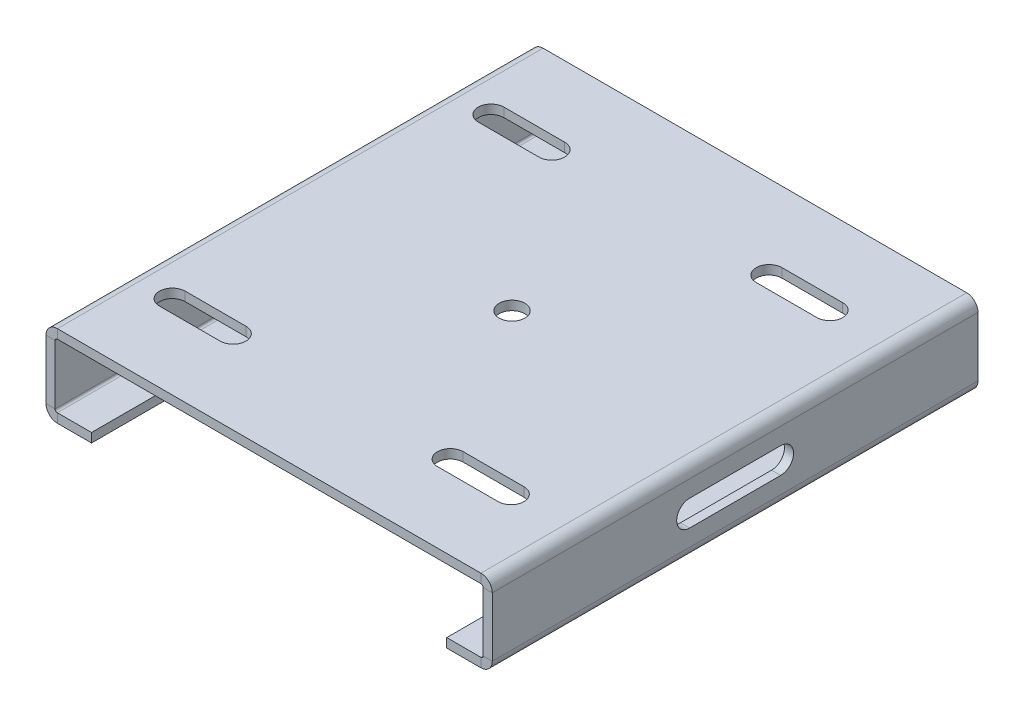
SolidWorks part; units mm, degrees
note: The reader was unsure of these and kept them because the rebuilt part matched: flange length of "Edge-Flange6", "Edge-Flange8".
ref_plane "Front Plane" through (0, 0, 0) normal (0, 0, 1) x (1, 0, 0)
ref_plane "Top Plane" through (0, 0, 0) normal (0, 1, 0) x (1, 0, 0)
ref_plane "Right Plane" through (0, 0, 0) normal (1, 0, 0) x (0, 0, -1)
sketch "Sketch1" plane through (0, 0, 0) normal (0, 1, 0) x (1, 0, 0)
  line L1 (-70.5, -80) -> (70.5, -80)
  line L2 (-70.5, -80) -> (-70.5, 80)
  line L3 (-70.5, 80) -> (70.5, 80)
  line L4 (70.5, -80) -> (70.5, 80)
  line L5 (-70.5, -80) -> (70.5, 80) construction
  line L6 (-70.5, 80) -> (70.5, -80) construction
  point P0 (0, 0)
  dimension "D1" = 141
  dimension "D2" = 160
base flange "Base-Flange3" sketch "Sketch1" thickness 3 reverse thickness direction no parameters "D1"=0.7366
edge flange "Edge-Flange6" sketch "Sketch58" flange profiles "Sketch58", "Sketch59" flange angle 90 flange length 24 flange position material outside bend radius 0.7366 thickness 3 relief rectangular parameters "D6"=10, "D8"=1
sketch "Sketch58" plane through (-70.5, -3, 0) normal (-1, 0, 0) x (0, 0, -1)
  line L0 (80, 0) -> (-80, 0) construction
  line L1 (80, 0) -> (-80, 0)
  line L2 (-80, 0) -> (-80, 21)
  line L3 (-80, 21) -> (80, 21)
  line L4 (80, 21) -> (80, 0)
sketch "Sketch59" plane through (70.5, -3, 0) normal (1, 0, 0) x (0, 0, 1)
  line L0 (80, 0) -> (-80, 0) construction
  line L1 (80, 0) -> (-80, 0)
  line L2 (-80, 0) -> (-80, 21)
  line L3 (-80, 21) -> (80, 21)
  line L4 (80, 21) -> (80, 0)
bend "EdgeBend11" bend radius 0.7366 bend angle 90 parameters "D5"=1
bend "EdgeBend12" bend radius 0.7366 bend angle 90 parameters "D5"=2
edge flange "Edge-Flange8" sketch "Sketch72" flange profiles "Sketch72", "Sketch73" flange angle 90 flange length 12 flange position material outside bend radius 0.7366 thickness 3 relief rectangular parameters "D6"=10, "D8"=1
sketch "Sketch72" plane through (-70.5, -24, 0) normal (0, -1, 0) x (0, 0, -1)
  line L0 (80, 0) -> (-80, 0) construction
  line L1 (80, 0) -> (-80, 0)
  line L2 (-80, 0) -> (-80, 12)
  line L3 (-80, 12) -> (80, 12)
  line L4 (80, 12) -> (80, 0)
sketch "Sketch73" plane through (70.5, -24, 0) normal (0, -1, 0) x (0, 0, 1)
  line L0 (80, 0) -> (-80, 0) construction
  line L1 (80, 0) -> (-80, 0)
  line L2 (-80, 0) -> (-80, 12)
  line L3 (-80, 12) -> (80, 12)
  line L4 (80, 12) -> (80, 0)
bend "EdgeBend15" bend radius 0.7366 bend angle 90 parameters "D5"=3
bend "EdgeBend16" bend radius 0.7366 bend angle 90 parameters "D5"=4
sketch "Sketch76" plane through (-73.5, 0, 0) normal (-1, 0, 0) x (0, 0, 1)
  line L0 (-15, -9.25) -> (15, -9.25)
  line L1 (-15, -17.75) -> (15, -17.75)
  circle A0 centre (-15, -13.5) radius 4.25
  circle A1 centre (15, -13.5) radius 4.25
extrude "Cut-Extrude1" cut sketch "Sketch76" against normal blind 10 contours A0 | A1 L0 A0 L1 | A1 normal cut yes
sketch "Sketch80" plane through (73.5, 0, 0) normal (1, 0, 0) x (0, 0, -1)
  line L0 (-15, -9.25) -> (15, -9.25)
  line L5 (-15, -17.75) -> (15, -17.75)
  circle A0 centre (-15, -13.5) radius 4.25
  circle A1 centre (15, -13.5) radius 4.25
extrude "Cut-Extrude3" cut sketch "Sketch80" against normal blind 10 contours A0 | A1 L0 A0 L5 | A1 normal cut yes
sketch "Sketch84" plane through (0, 0, 0) normal (0, 1, 0) x (1, 0, 0)
  line L4 (42.1906, -52.5) -> (32.1906, -52.5)
  line L5 (42.1906, -52.5) -> (52.1906, -52.5)
  line L6 (-59.3847, -56.75) -> (-39.3847, -56.75)
  line L7 (-59.3847, -48.25) -> (-39.3847, -48.25)
  line L8 (32.1906, -56.75) -> (52.1906, -56.75)
  line L9 (32.1906, -48.25) -> (52.1906, -48.25)
  line L12 (-59.3847, 48.25) -> (-39.3847, 48.25)
  line L13 (-59.3847, 56.75) -> (-39.3847, 56.75)
  line L16 (32.1906, 48.25) -> (52.1906, 48.25)
  line L17 (32.1906, 56.75) -> (52.1906, 56.75)
  circle A0 centre (-59.3847, -52.5) radius 4.25
  circle A1 centre (-39.3847, -52.5) radius 4.25
  circle A2 centre (32.1906, -52.5) radius 4.25
  circle A3 centre (52.1906, -52.5) radius 4.25
  circle A4 centre (-59.3847, 52.5) radius 4.25
  circle A5 centre (-39.3847, 52.5) radius 4.25
  circle A6 centre (32.1906, 52.5) radius 4.25
  circle A7 centre (52.1906, 52.5) radius 4.25
extrude "Cut-Extrude4" cut sketch "Sketch84" against normal blind 10
sketch "Sketch85" plane through (0, -3, 0) normal (0, -1, 0) x (1, 0, 0)
  line L0 (-70.5, -80) -> (70.5, 80) construction
  circle A0 centre (0, 0) radius 4.25
extrude "Cut-Extrude5" cut sketch "Sketch85" against normal blind 10 normal cut yes
sketch "Bend-Lines5" [suppressed] plane through (0, 0, 0) normal (0, 1, 0) x (1, 0, 0)
sketch "Bounding-Box5" [suppressed] plane through (0, 0, 0) normal (0, 1, 0) x (1, 0, 0)
sheet metal parameters "Sheet-Metal7" thickness 3 parameters "D1"=0.7366
flat pattern "Flat-Pattern7" [suppressed]
sketch "Bend-Lines6" plane through (0, 0, 0) normal (0, 1, 0) x (1, 0, 0)
sketch3d "Bounding-Box6" [suppressed]
  line L0 (-70.5, -80, 0) -> (-70.5, 80, 0) construction
  line L1 (70.5, -80, 0) -> (70.5, 80, 0) construction
  line L2 (-70.5, -80, 0) -> (70.5, -80, 0) construction
  line L3 (-70.5, 80, 0) -> (70.5, 80, 0) construction
sheet metal parameters "Sheet-Metal9" thickness 3 parameters "D1"=0.7366
flat pattern "Flat-Pattern7"
sketch "Bend-Lines6" plane through (0, 0, 0) normal (0, 1, 0) x (1, 0, 0)
  line L0 (71.52, -80) -> (71.52, 80) construction
  line L1 (-71.52, 80) -> (-71.52, -80) construction
  line L2 (71.52, -80) -> (71.52, 80) construction
  line L3 (-71.52, 80) -> (-71.52, -80) construction
sketch3d "Bounding-Box6" [suppressed]
  line L0 (93.54, 80, 0) -> (-93.54, 80, 0) construction
  line L1 (93.54, -80, 0) -> (-93.54, -80, 0) construction
  line L2 (93.54, 80, 0) -> (93.54, -80, 0) construction
  line L3 (-93.54, 80, 0) -> (-93.54, -80, 0) construction
bend of the flat pattern "Flatten-<EdgeBend11>1"
bend of the flat pattern "Flatten-<EdgeBend12>1"
sheet metal parameters "Sheet-Metal11" thickness 3 parameters "D1"=0.7366
flat pattern "Flat-Pattern7"
sketch "Bend-Lines6" plane through (0, 0, 0) normal (0, 1, 0) x (1, 0, 0)
  line L0 (71.52, -80) -> (71.52, 80) construction
  line L1 (-71.52, 80) -> (-71.52, -80) construction
  line L2 (71.52, -80) -> (71.52, 80) construction
  line L3 (-71.52, 80) -> (-71.52, -80) construction
  line L4 (94.5601, -80) -> (94.5601, 80) construction
  line L5 (-94.5601, 80) -> (-94.5601, -80) construction
  line L6 (94.5601, -80) -> (94.5601, 80) construction
  line L7 (-94.5601, 80) -> (-94.5601, -80) construction
sketch3d "Bounding-Box6" [suppressed]
  line L0 (107.5801, 80, 0) -> (-107.5801, 80, 0) construction
  line L1 (107.5801, -80, 0) -> (-107.5801, -80, 0) construction
  line L2 (107.5801, 80, 0) -> (107.5801, -80, 0) construction
  line L3 (-107.5801, 80, 0) -> (-107.5801, -80, 0) construction
bend of the flat pattern "Flatten-<EdgeBend11>1"
bend of the flat pattern "Flatten-<EdgeBend12>1"
bend of the flat pattern "Flatten-<EdgeBend15>1"
bend of the flat pattern "Flatten-<EdgeBend16>1"
sheet metal parameters "Sheet-Metal12" thickness 3 parameters "D1"=0.7366
flat pattern "Flat-Pattern7" [suppressed]
sketch "Bend-Lines6" plane through (0, 0, 0) normal (0, 1, 0) x (1, 0, 0)
  line L0 (71.52, -80) -> (71.52, 80) construction
  line L1 (-71.52, 80) -> (-71.52, -80) construction
  line L2 (71.52, -80) -> (71.52, 80) construction
  line L3 (-71.52, 80) -> (-71.52, -80) construction
  line L4 (94.5601, -80) -> (94.5601, 80) construction
  line L5 (-94.5601, 80) -> (-94.5601, -80) construction
  line L6 (94.5601, -80) -> (94.5601, 80) construction
  line L7 (-94.5601, 80) -> (-94.5601, -80) construction
sketch3d "Bounding-Box6" [suppressed]
  line L0 (107.5801, 80, 0) -> (-107.5801, 80, 0) construction
  line L1 (107.5801, -80, 0) -> (-107.5801, -80, 0) construction
  line L2 (107.5801, 80, 0) -> (107.5801, -80, 0) construction
  line L3 (-107.5801, 80, 0) -> (-107.5801, -80, 0) construction
bend of the flat pattern "Flatten-<EdgeBend11>1"
bend of the flat pattern "Flatten-<EdgeBend12>1"
bend of the flat pattern "Flatten-<EdgeBend15>1"
bend of the flat pattern "Flatten-<EdgeBend16>1"
sketch "Sketch80-1" [suppressed] plane through (69.54, 0, 0) normal (0, 1, 0) x (0, 0, -1)
  line L0 (-15, -9.25) -> (15, -9.25)
  line L5 (-15, -17.75) -> (15, -17.75)
  circle A0 centre (-15, -13.5) radius 4.25
  circle A1 centre (15, -13.5) radius 4.25
sheet metal parameters "Sheet-Metal14" thickness 3 parameters "D1"=0.7366
flat pattern "Flat-Pattern7" [suppressed]
sketch "Bend-Lines6" plane through (0, 0, 0) normal (0, 1, 0) x (1, 0, 0)
  line L0 (71.52, -80) -> (71.52, 80) construction
  line L1 (-71.52, 80) -> (-71.52, -80) construction
  line L2 (71.52, -80) -> (71.52, 80) construction
  line L3 (-71.52, 80) -> (-71.52, -80) construction
  line L4 (94.5601, -80) -> (94.5601, 80) construction
  line L5 (-94.5601, 80) -> (-94.5601, -80) construction
  line L6 (94.5601, -80) -> (94.5601, 80) construction
  line L7 (-94.5601, 80) -> (-94.5601, -80) construction
sketch3d "Bounding-Box6" [suppressed]
  line L0 (107.5801, 80, 0) -> (-107.5801, 80, 0) construction
  line L1 (107.5801, -80, 0) -> (-107.5801, -80, 0) construction
  line L2 (107.5801, 80, 0) -> (107.5801, -80, 0) construction
  line L3 (-107.5801, 80, 0) -> (-107.5801, -80, 0) construction
bend of the flat pattern "Flatten-<EdgeBend11>1"
bend of the flat pattern "Flatten-<EdgeBend12>1"
bend of the flat pattern "Flatten-<EdgeBend15>1"
bend of the flat pattern "Flatten-<EdgeBend16>1"
sketch "Sketch80-1" [suppressed] plane through (69.54, 0, 0) normal (0, 1, 0) x (0, 0, -1)
  line L0 (-15, -9.25) -> (15, -9.25)
  line L5 (-15, -17.75) -> (15, -17.75)
  circle A0 centre (-15, -13.5) radius 4.25
  circle A1 centre (15, -13.5) radius 4.25
sheet metal parameters "Sheet-Metal15" thickness 3 parameters "D1"=0.7366
flat pattern "Flat-Pattern7" [suppressed]
sketch "Bend-Lines6" plane through (0, 0, 0) normal (0, 1, 0) x (1, 0, 0)
  line L0 (71.52, -80) -> (71.52, 80) construction
  line L1 (-71.52, 80) -> (-71.52, -80) construction
  line L2 (71.52, -80) -> (71.52, 80) construction
  line L3 (-71.52, 80) -> (-71.52, -80) construction
  line L4 (94.5601, -80) -> (94.5601, 80) construction
  line L5 (-94.5601, 80) -> (-94.5601, -80) construction
  line L6 (94.5601, -80) -> (94.5601, 80) construction
  line L7 (-94.5601, 80) -> (-94.5601, -80) construction
sketch3d "Bounding-Box6" [suppressed]
  line L0 (107.5801, 80, 0) -> (-107.5801, 80, 0) construction
  line L1 (107.5801, -80, 0) -> (-107.5801, -80, 0) construction
  line L2 (107.5801, 80, 0) -> (107.5801, -80, 0) construction
  line L3 (-107.5801, 80, 0) -> (-107.5801, -80, 0) construction
bend of the flat pattern "Flatten-<EdgeBend11>1"
bend of the flat pattern "Flatten-<EdgeBend12>1"
bend of the flat pattern "Flatten-<EdgeBend15>1"
bend of the flat pattern "Flatten-<EdgeBend16>1"
sketch "Sketch80-1" [suppressed] plane through (69.54, 0, 0) normal (0, 1, 0) x (0, 0, -1)
  line L0 (-15, -9.25) -> (15, -9.25)
  line L5 (-15, -17.75) -> (15, -17.75)
  circle A0 centre (-15, -13.5) radius 4.25
  circle A1 centre (15, -13.5) radius 4.25
sheet metal parameters "Sheet-Metal16" thickness 3 parameters "D1"=0.7366
flat pattern "Flat-Pattern7" [suppressed]
sketch "Bend-Lines6" plane through (0, 0, 0) normal (0, 1, 0) x (1, 0, 0)
  line L0 (71.52, -80) -> (71.52, 80) construction
  line L1 (-71.52, 80) -> (-71.52, -80) construction
  line L2 (71.52, -80) -> (71.52, 80) construction
  line L3 (-71.52, 80) -> (-71.52, -80) construction
  line L4 (94.5601, -80) -> (94.5601, 80) construction
  line L5 (-94.5601, 80) -> (-94.5601, -80) construction
  line L6 (94.5601, -80) -> (94.5601, 80) construction
  line L7 (-94.5601, 80) -> (-94.5601, -80) construction
sketch3d "Bounding-Box6" [suppressed]
  line L0 (107.5801, 80, 0) -> (-107.5801, 80, 0) construction
  line L1 (107.5801, -80, 0) -> (-107.5801, -80, 0) construction
  line L2 (107.5801, 80, 0) -> (107.5801, -80, 0) construction
  line L3 (-107.5801, 80, 0) -> (-107.5801, -80, 0) construction
bend of the flat pattern "Flatten-<EdgeBend11>1"
bend of the flat pattern "Flatten-<EdgeBend12>1"
bend of the flat pattern "Flatten-<EdgeBend15>1"
bend of the flat pattern "Flatten-<EdgeBend16>1"
sketch "Sketch80-1" [suppressed] plane through (69.54, 0, 0) normal (0, 1, 0) x (0, 0, -1)
  line L0 (-15, -9.25) -> (15, -9.25)
  line L5 (-15, -17.75) -> (15, -17.75)
  circle A0 centre (-15, -13.5) radius 4.25
  circle A1 centre (15, -13.5) radius 4.25
